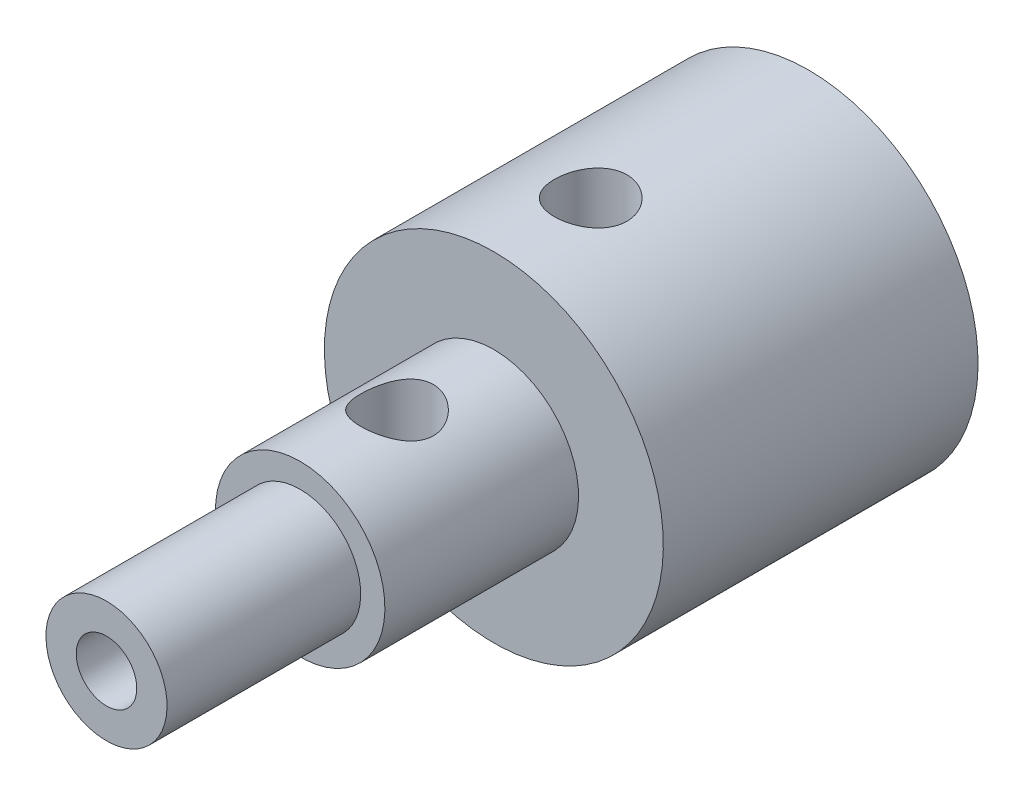
SolidWorks part; units mm, degrees
material "1060 Alloy"
ref_plane "Front Plane" through (0, 0, 0) normal (0, 0, 1) x (1, 0, 0)
ref_plane "Top Plane" through (0, 0, 0) normal (0, 1, 0) x (1, 0, 0)
ref_plane "Right Plane" through (0, 0, 0) normal (1, 0, 0) x (0, 0, -1)
sketch "Sketch1" plane through (0, 0, 0) normal (1, 0, 0) x (0, 0, -1)
  line L0 (0, 0) -> (0, 2.5)
  line L1 (16, 3.5) -> (8, 3.5)
  line L2 (16, 3.5) -> (16, 7)
  line L3 (16.5772, 0) -> (18.5, 3.2)
  line L4 (18.5, 3.2) -> (29, 3.2)
  line L5 (16, 7) -> (29, 7)
  line L6 (29, 3.2) -> (29, 7)
  line L7 (16.5772, 0) -> (0, 0)
  line L8 (8, 3.5) -> (8, 2.5)
  line L9 (8, 2.5) -> (0, 2.5)
  dimension "D1" = 2.5
  dimension "D2" = 8
  dimension "D3" = 3.2
  dimension "D4" = 2.5
  dimension "D5" = 13
  dimension "D6" = 7
  dimension "D7" = 121
  dimension "D8" = 3.5
  dimension "D9" = 8
revolve "Revolve1" add sketch "Sketch1" angle 360 about L7
sketch "Sketch2" plane through (0, 0, 0) normal (0, 1, 0) x (1, 0, 0)
  line L0 (-3.5, 16) -> (3.5, 16) construction
  line L1 (-7, 16) -> (7, 16) construction
  circle A0 centre (0, 20) radius 1.5
  circle A1 centre (0, 12) radius 1.5
  dimension "D2" = 3
  dimension "D3" = 3
  dimension "D1" = 4
  dimension "D4" = 4
extrude "Cut-Extrude1" cut sketch "Sketch2" against normal up to next and the other way up to next
sketch "Sketch4" plane through (0, 0, 0) normal (0, 0, 1) x (1, 0, 0)
  circle A0 centre (0, 0) radius 1.25
  dimension "D1" = 2.5
extrude "Cut-Extrude2" cut sketch "Sketch4" against normal blind 10
ref_plane "Plane1" through (0, 0, -24) normal (0, 0, -1) x (-1, 0, 0)
